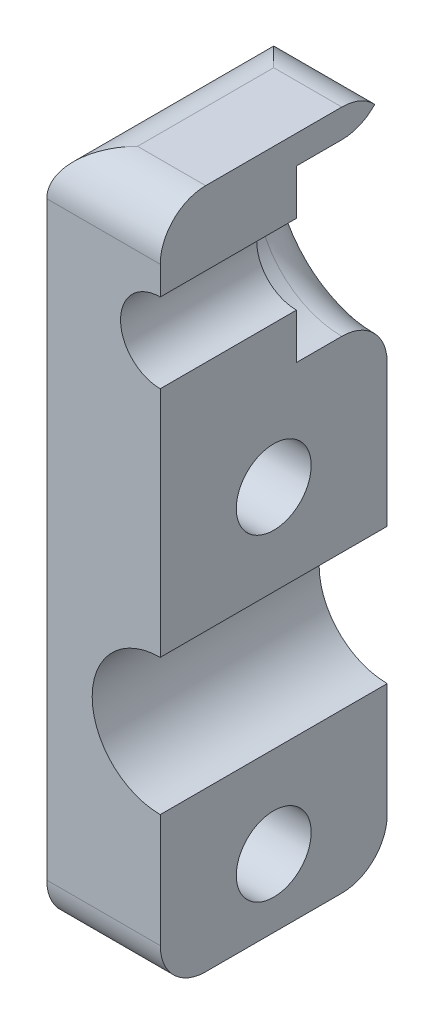
SolidWorks part; units mm, degrees
ref_plane "Front Plane" through (0, 0, 0) normal (0, 0, 1) x (1, 0, 0)
ref_plane "Top Plane" through (0, 0, 0) normal (0, 1, 0) x (1, 0, 0)
ref_plane "Right Plane" through (0, 0, 0) normal (1, 0, 0) x (0, 0, -1)
sketch "草圖1" plane through (0, 0, 0) normal (0, 0, 1) x (1, 0, 0)
  line L1 (5, -10) -> (-5, -10)
  line L2 (5, -10) -> (5, 10)
  line L3 (5, 10) -> (-5, 10)
  line L4 (-5, -10) -> (-5, 10)
  line L5 (5, -10) -> (-5, 10) construction
  line L6 (5, 10) -> (-5, -10) construction
  circle A0 centre (0, 0) radius 3
  point P0 (0, 0)
  dimension "D3" = 6
  dimension "D1" = 10
  dimension "D2" = 20
extrude "填料-伸長1" add sketch "草圖1" along normal blind 10
sketch "草圖2" plane through (-5, 0, 0) normal (-1, 0, 0) x (0, 0, 1)
  line L0 (0, 10) -> (0, -10) construction
  line L1 (10, 10) -> (0, 10) construction
  line L2 (10, -10) -> (0, -10) construction
  circle A0 centre (5, 7) radius 1.65
  circle A1 centre (5, -7) radius 1.65
  dimension "D1" = 3.3
  dimension "D2" = 5
  dimension "D3" = 3
  dimension "D4" = 3
extrude "除料-伸長1" cut sketch "草圖2" against normal through all
sketch "草圖3" plane through (0, 0, 10) normal (0, 0, 1) x (1, 0, 0)
  line L0 (5, 10) -> (-5, 10) construction
  line L1 (0, 10) -> (12.8527, 10)
  line L2 (0, 10) -> (0, -10.2796)
  line L3 (0, -10.2796) -> (12.8527, -10.2796)
  line L4 (12.8527, 10) -> (12.8527, -10.2796)
extrude "除料-伸長2" cut sketch "草圖3" against normal through all
sketch "草圖5" plane through (0, 0, 10) normal (0, 0, 1) x (1, 0, 0)
  line L0 (0, 10) -> (0, 13.25)
  line L1 (-5, 10) -> (0, 10)
  line L2 (-5, 10) -> (-5, 20)
  line L3 (-5, 20) -> (0, 20)
  line L5 (0, 16.75) -> (0, 20)
  line L6 (0, 10) -> (0, 3) construction
  arc A0 (0, 16.75) -> (0, 13.25) centre (0, 15) ccw
  dimension "D2" = 3.5
  dimension "D3" = 5
  dimension "D1" = 10
extrude "填料-伸長2" add sketch "草圖5" against normal through all
fillet "圓角1" radius 2 5 edges at (-2.5, 20, 10) (-2.5, 20, 0) (-2.5, -10, 0) (-2.5, -10, 10) (-5, 20, 5)
sketch "草圖6" plane through (0, 0, 10) normal (0, 0, 1) x (1, 0, 0)
  circle A0 centre (0, 15) radius 3.75
  dimension "D1" = 7.5
extrude "除料-伸長3" cut sketch "草圖6" along normal blind 4 from surface starting at face at (-1.8437, 6.25, 0)
fillet "圓角2" radius 2 1 edges at (-3.5576, 13.8141, 0)
